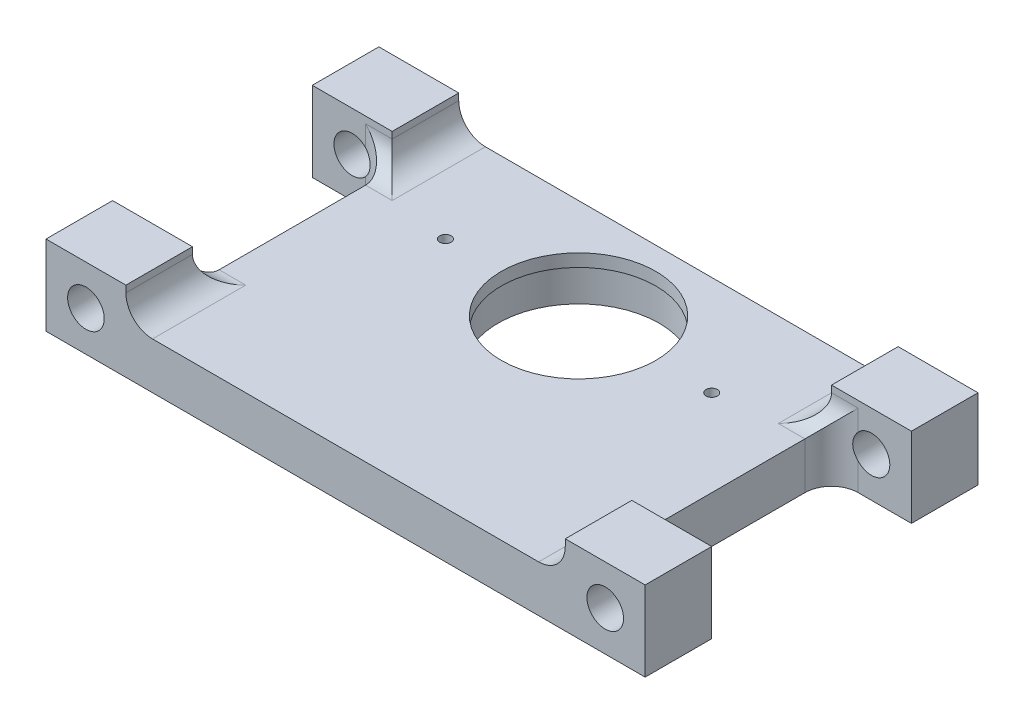
SolidWorks part; units mm, degrees
ref_plane "Спереди" through (0, 0, 0) normal (0, 0, 1) x (1, 0, 0)
ref_plane "Сверху" through (0, 0, 0) normal (0, 1, 0) x (1, 0, 0)
ref_plane "Справа" through (0, 0, 0) normal (1, 0, 0) x (0, 0, -1)
sketch "Эскиз1" plane through (0, 0, 0) normal (0, 1, 0) x (1, 0, 0)
  line L0 (-33, 0) -> (33, 0) construction
  line L1 (-33, -35) -> (33, -35)
  line L3 (0, 17) -> (0, -17) construction
  line L5 (-33, -35) -> (-33, 15)
  line L7 (-9.5671, -23.097) -> (0, 0) construction
  line L8 (17.0671, -23.097) -> (17.0671, 0) construction
  line L10 (0, 0) -> (9.5671, -23.097) construction
  line L11 (33, -35) -> (33, 15)
  line L12 (33, 15) -> (-33, 15)
  circle A0 centre (0, 0) radius 12 construction
  circle A1 centre (0, 0) radius 12.1
  arc A3 (-9.5671, -23.097) -> (9.5671, -23.097) centre (0, 0) ccw construction
  circle A4 centre (-9.5671, -23.097) radius 7 construction
  circle A5 centre (9.5671, -23.097) radius 7 construction
  arc A6 (-6.697, -16.1679) -> (6.697, -16.1679) centre (0, 0) ccw construction
  arc A8 (-12.4372, -30.0261) -> (-6.697, -16.1679) centre (-9.5671, -23.097) cw construction
  arc A10 (12.4372, -30.0261) -> (6.697, -16.1679) centre (9.5671, -23.097) ccw construction
  arc A13 (-12.4372, -30.0261) -> (12.4372, -30.0261) centre (0, 0) ccw construction
  circle A15 centre (0, 0) radius 17 construction
  point P14 (0, 12)
  point P20 (25, -20)
  point P30 (0, 15)
  dimension "D1" = 24
  dimension "D7" = 20
  dimension "D2" = 25
  dimension "D8" = 45
  dimension "D6" = 25
  dimension "D5" = 15
  dimension "D10" = 8
  dimension "D11" = 5
  dimension "D9" = 14
  dimension "D12" = 3
  dimension "D3" = 0.5
  dimension "tolerance" = 0.1
extrude "Бобышка-Вытянуть1" add sketch "Эскиз1" along normal blind 7
ref_plane "Плоскость1" through (0, 5, 0) normal (0, -1, 0) x (-1, 0, 0)
ref_plane "Плоскость3" through (0, 0, 0) normal (-1, 0, 0) x (0, 0, 1)
ref_plane "Плоскость4" through (0, 0, 10) normal (0, 0, -1) x (-1, 0, 0)
sketch "Эскиз7" plane through (0, 7, 0) normal (0, 1, 0) x (1, 0, 0)
  circle A0 centre (0, 0) radius 12.1 construction
  circle A1 centre (0, 0) radius 12.1
  circle A2 centre (0, 0) radius 11.6
  dimension "D1" = 0.5
extrude "Бобышка-Вытянуть2" add sketch "Эскиз7" against normal offset from surface (1.9 mm away) 0.1 up to plane "Плоскость1"
sketch "Эскиз14" plane through (0, 0, -15) normal (0, 0, -1) x (-1, 0, 0)
  line L1 (-33, 0) -> (-33, 12)
  line L2 (-33, 12) -> (-45, 12)
  line L3 (-45, 12) -> (-45, 0)
  line L4 (-45, 0) -> (-33, 0)
  line L5 (-33, 7) -> (-33, 0) construction
  circle A0 centre (-39, 6) radius 6 construction
  dimension "D1" = 12
extrude "Бобышка-Вытянуть4" add sketch "Эскиз14" against normal blind 10
mirror "Зеркальное отражение10" about plane through (0, 0, 0) normal (-1, 0, 0) of "Бобышка-Вытянуть4"
mirror "Зеркальное отражение17" about plane through (0, 0, 10) normal (0, 0, -1) of "Зеркальное отражение10", "Бобышка-Вытянуть4"
fillet "Скругление9" radius 4 4 edges at (33, 7, 30) (-33, 7, 30)
hole_wizard "Отверстие с зазором M52" positions "Эскиз16" profile "Эскиз15" hole size "M5" standard "Ansi Metric" end condition through all
sketch "Эскиз16" plane through (12.8512, -2.6573, -15) normal (0, 0, -1) x (-1, 0, 0)
  line L0 (51.8512, 14.6573) -> (51.8512, 2.6573) construction
  line L7 (45.8512, 14.6573) -> (57.8512, 14.6573) construction
  line L10 (-32.1488, 2.6573) -> (57.8512, 2.6573) construction
  point P0 (51.8512, 8.6573)
sketch "Эскиз15" plane through (-39, 6, -15) normal (1, 0, 0) x (0, 1, 0)
  line L0 (0, 0) -> (0, 50)
  line L1 (0, 50) -> (2.75, 50)
  line L2 (2.75, 50) -> (2.75, 0)
  line L5 (2.75, 0) -> (0, 0)
  line L11 (0, -6.35) -> (0, 107.95) construction
  dimension "Диаметр сквозного отверстия" = 5.5
  dimension "Глубина сквозного отверстия" = 50
mirror "Зеркальное отражение11" about plane through (0, 0, 0) normal (-1, 0, 0) of "Отверстие с зазором M52"
mirror "Зеркальное отражение18" about plane through (0, 0, 10) normal (0, 0, -1) of "Зеркальное отражение11", "Отверстие с зазором M52"
sketch "Эскиз17" plane through (0, 0, -5) normal (0, 0, 1) x (1, 0, 0)
  line L0 (-43.25, 3.5463) -> (-39, 1.0925)
  line L1 (-34.75, 3.5463) -> (-34.75, 8.4537)
  line L2 (-34.75, 8.4537) -> (-39, 10.9075)
  line L3 (-39, 10.9075) -> (-43.25, 8.4537)
  line L4 (-43.25, 8.4537) -> (-43.25, 3.5463)
  line L5 (-39, 1.0925) -> (-34.75, 3.5463)
  line L6 (-45, 12) -> (-45, 0) construction
  circle A0 centre (-39, 6) radius 4.25 construction
  dimension "D1" = 8.5
extrude "Вырез-Вытянуть4" [suppressed] cut sketch "Эскиз17" against normal blind 2
mirror "Зеркальное отражение12" [suppressed] about plane through (0, 0, 0) normal (-1, 0, 0)
sketch "Эскиз18" plane through (0, 7, 0) normal (0, 1, 0) x (1, 0, 0)
  line L3 (0, 0) -> (0, -17.5) construction
  arc A0 (-6.697, -16.1679) -> (-12.4372, -30.0261) centre (-9.5671, -23.097) ccw construction
  arc A1 (-12.4372, -30.0261) -> (12.4372, -30.0261) centre (0, 0) ccw
  arc A3 (-6.697, -16.1679) -> (6.697, -16.1679) centre (0, 0) ccw construction
  arc A6 (-6.697, -16.1679) -> (-12.4372, -30.0261) centre (-9.5671, -23.097) ccw
  arc A8 (6.697, -16.1679) -> (12.4372, -30.0261) centre (9.5671, -23.097) cw
  arc A9 (-6.697, -16.1679) -> (6.697, -16.1679) centre (0, 0) ccw
extrude "Вырез-Вытянуть5" [suppressed] cut sketch "Эскиз18" against normal through all
hole_wizard "Зенковка для  винта с плоской головкой M51" [suppressed] positions "Эскиз23" profile "Эскиз22" countersink size "M5" standard "Ansi Metric"
sketch "Эскиз23" plane through (-24.0424, 0, 23.4075) normal (0, 1, 0) x (1, 0, 0)
  line L1 (24.0424, 23.4075) -> (24.0424, 5.9075) construction
  line L2 (24.0424, 23.4075) -> (24.0424, 5.9075) construction
  point P0 (49.0424, 3.4075)
  point P2 (-0.9576, 3.4075)
sketch "Эскиз22" plane through (25, 0, 20) normal (1, 0, 0) x (0, 0, -1)
  line L0 (0, 0) -> (0, 12)
  line L1 (0, 12) -> (2.75, 12)
  line L2 (2.75, 12) -> (2.75, 2.75)
  line L3 (2.75, 2.75) -> (5.5, 0)
  line L5 (5.5, 0) -> (0, 0)
  line L6 (-2.75, 2.75) -> (-5.5, 0) construction
  line L11 (0, -6.35) -> (0, 107.95) construction
  dimension "Диаметр сквозного отверстия" = 5.5
  dimension "Глубина сквозного отверстия" = 12
  dimension "Диаметр передней зенковки" = 11
  dimension "Угол передней зенковки" = 90
mirror "Зеркальное отражение19" [suppressed] about plane through (0, 0, 10) normal (0, 0, -1)
sketch "Эскиз24" [suppressed] plane through (0, 8, 0) normal (0, 1, 0) x (1, 0, 0)
  line L0 (0, 0) -> (0, -17.5) construction
  line L1 (0, 0) -> (0, -17.5) construction
  circle A0 centre (25, -20) radius 2.75 construction
  circle A1 centre (25, -20) radius 2.75
  circle A2 centre (-25, -20) radius 2.75 construction
  circle A3 centre (25, -20) radius 4.25
  circle A6 centre (-25, -20) radius 4.25
  circle A7 centre (-25, -20) radius 2.75
  dimension "D1" = 1.5
  dimension "D2" = 1.5
extrude "Бобышка-Вытянуть5" [suppressed] add sketch "Эскиз24" along normal blind 0.5
fillet "Скругление10" radius 4 8 edges at (-31, 7, -5) (31, 7, -5) (33, 3.5, 25) (31, 7, 25) (-31, 7, 25) (-33, 3.5, 25)
sketch "Эскиз19" [suppressed] plane through (0, 8, 0) normal (0, 1, 0) x (1, 0, 0)
  line L0 (0, 20) -> (0, -33) construction
  line L1 (45, 20) -> (-45, 20) construction
  line L2 (-45, -33) -> (45, -33) construction
  line L11 (-28, 6) -> (-28, -17)
  line L12 (-28, 16) -> (-28, 4)
  line L14 (45, 16) -> (-45, 16)
  line L15 (-10.6132, 16) -> (-28, 16)
  line L16 (-2, -19.0955) -> (-2, -23)
  line L17 (-45, -23) -> (45, -23)
  line L18 (-28, -23) -> (-2, -23)
  line L19 (-2, 20) -> (-2, -33) construction
  line L20 (0, 0) -> (-33, 0) construction
  line L21 (-33, 6) -> (-33, -17) construction
  line L22 (-18.7787, 4) -> (-28, 4)
  line L23 (-18.7787, -4) -> (-28, -4)
  line L24 (0, 4) -> (-33, 4) construction
  line L25 (0, -4) -> (-33, -4) construction
  line L26 (-28, -4) -> (-28, -23)
  arc A1 (-10.6132, 16) -> (-18.7787, 4) centre (0, 0) ccw
  circle A2 centre (0, 0) radius 19.2
  arc A3 (-18.7787, -4) -> (-2, -19.0955) centre (0, 0) ccw
  dimension "D1" = 3
  dimension "D2" = 5
  dimension "D3" = 4
  dimension "D4" = 10
  dimension "D5" = 2
  dimension "D6" = 4
  dimension "D7" = 4
extrude "Вырез-Вытянуть6" [suppressed] cut sketch "Эскиз19" against normal blind 6
mirror "Зеркальное отражение14" [suppressed] about plane through (0, 0, 0) normal (-1, 0, 0)
hole_wizard "Сверление под метчик M2x0.41" [suppressed] positions "Эскиз26" profile "Эскиз25" hole size "M2x0.4" standard "Ansi Metric"
sketch "Эскиз26" plane through (0, 8, 0) normal (0, 1, 0) x (1, 0, 0)
  line L0 (0, 0) -> (0, -17.5) construction
  line L1 (0, 0) -> (0, -17.5) construction
  point P0 (-14.5, 0)
  point P2 (14.5, 0)
  dimension "D1" = 14.5
sketch "Эскиз25" plane through (-14.5, 8, 0) normal (1, 0, 0) x (0, 0, 1)
  line L0 (0, 0) -> (0, 8)
  line L1 (0, 8) -> (0.8, 8)
  line L2 (0.8, 8) -> (0.8, 0)
  line L5 (0.8, 0) -> (0, 0)
  line L11 (0, -6.35) -> (0, 107.95) construction
  dimension "Диаметр сквозного отверстия" = 1.6
  dimension "Глубина сквозного отверстия" = 8
chamfer "Фаска1" [suppressed] distance 0.5 angle 45
sketch "Эскиз27" plane through (0, 7, 0) normal (0, 1, 0) x (1, 0, 0)
  circle A0 centre (0, 0) radius 13.25
  dimension "D1" = 26.5
extrude "Вырез-Вытянуть7" [suppressed] cut sketch "Эскиз27" against normal blind 0.5
sketch "Sketch1" plane through (0, 7, 0) normal (0, 1, 0) x (1, 0, 0)
  line L0 (-20, 0) -> (20, 0) construction
  line L1 (0, 0) -> (0, 11.6) construction
  circle A0 centre (20, 0) radius 0.85
  circle A1 centre (0, 0) radius 11.6 construction
  circle A2 centre (-20, 0) radius 0.85
  dimension "D2" = 1.7
  dimension "D1" = 20
extrude "Cut-Extrude1" cut sketch "Sketch1" against normal blind 10
